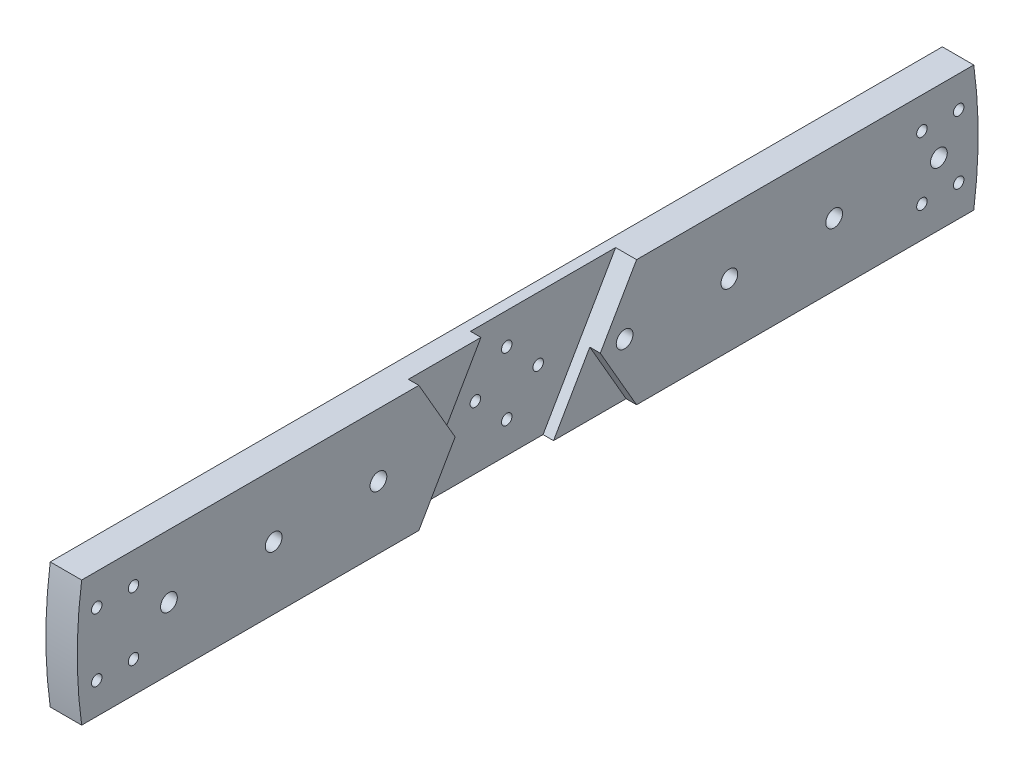
SolidWorks part; units mm, degrees
ref_plane "Front Plane" through (0, 0, 0) normal (0, 0, 1) x (1, 0, 0)
ref_plane "Top Plane" through (0, 0, 0) normal (0, 1, 0) x (1, 0, 0)
ref_plane "Right Plane" through (0, 0, 0) normal (1, 0, 0) x (0, 0, -1)
sketch "Sketch1" plane through (0, 0, 0) normal (1, 0, 0) x (0, 0, -1)
  circle A0 centre (0, 0) radius 273.05
  point P0 (0, 0)
  dimension "D1" = 546.1
curve "Helix/Spiral1"
sketch "Sketch2" plane through (0, 0, 0) normal (1, 0, 0) x (0, 0, -1)
  line L0 (-273.05, 0) -> (273.05, 0) construction
  line L1 (-270.3788, -38.1) -> (270.3788, -38.1)
  line L3 (-270.3788, 38.1) -> (270.3788, 38.1)
  line L4 (270.3788, -38.1) -> (270.3788, 38.1) construction
  line L5 (-270.3788, -38.1) -> (270.3788, 38.1) construction
  line L6 (-270.3788, 38.1) -> (270.3788, -38.1) construction
  line L7 (273.05, 0) -> (228.6, 0) construction
  line L8 (38.1, -38.1) -> (-38.1, -38.1)
  line L9 (38.1, -38.1) -> (38.1, 38.1)
  line L10 (38.1, 38.1) -> (-38.1, 38.1)
  line L11 (-38.1, -38.1) -> (-38.1, 38.1)
  line L12 (38.1, -38.1) -> (-38.1, 38.1) construction
  line L13 (38.1, 38.1) -> (-38.1, -38.1) construction
  line L14 (226.3636, 31.8977) -> (270.3788, 38.1)
  line L16 (273.05, 0) -> (250.825, 0)
  line L17 (250.825, 0) -> (228.6, 0)
  line L18 (0, 0) -> (238.9495, -19.1108) construction
  line L19 (0, 0) -> (-19.1108, -238.9495) construction
  line L20 (0, 38.1) -> (0, -38.1) construction
  line L21 (0, 0) -> (38.1, 38.1)
  line L28 (19.05, -19.05) -> (-19.05, -19.05)
  line L29 (19.05, -19.05) -> (19.05, 19.05)
  line L30 (19.05, 19.05) -> (-19.05, 19.05)
  line L31 (-19.05, -19.05) -> (-19.05, 19.05)
  line L32 (19.05, -19.05) -> (-19.05, 19.05) construction
  line L33 (19.05, 19.05) -> (-19.05, -19.05) construction
  circle A0 centre (0, 0) radius 273.05 construction
  circle A3 centre (185.7375, 0) radius 5.08
  circle A4 centre (122.2375, 0) radius 5.08
  circle A6 centre (-90.4875, 0) radius 5.08
  circle A7 centre (-153.9875, 0) radius 5.08
  circle A8 centre (-217.4875, 0) radius 5.08
  circle A9 centre (0, 0) radius 273.05
  circle A10 centre (0, 0) radius 228.6
  arc A11 (247.9144, -38.1) -> (250.825, 0) centre (0, 0) ccw
  arc A12 (236.6653, -38.1) -> (239.7125, 0) centre (0, 0) ccw
  arc A13 (259.1518, -38.1) -> (261.9375, 0) centre (0, 0) ccw
  circle A14 centre (238.9495, -19.1108) radius 3.175
  circle A15 centre (261.2401, -19.1009) radius 3.175
  circle A16 centre (238.9495, 19.1108) radius 3.175
  circle A17 centre (261.2401, 19.1009) radius 3.175
  circle A18 centre (19.1009, -261.2401) radius 3.175
  circle A19 centre (19.1108, -238.9495) radius 3.175
  circle A20 centre (-19.1108, -238.9495) radius 3.175
  circle A21 centre (-19.1009, -261.2401) radius 3.175
  circle A26 centre (-19.1009, 261.2401) radius 3.175
  circle A27 centre (-19.1108, 238.9495) radius 3.175
  circle A28 centre (19.1108, 238.9495) radius 3.175
  circle A29 centre (19.1009, 261.2401) radius 3.175
  circle A30 centre (-19.05, 0) radius 3.175
  circle A31 centre (0, 19.05) radius 3.175
  circle A32 centre (19.05, 0) radius 3.175
  circle A33 centre (0, -19.05) radius 3.175
  circle A34 centre (-238.9495, 19.1108) radius 3.175 [skipped]
  circle A35 centre (-261.2401, 19.1009) radius 3.175 [skipped]
  circle A36 centre (-261.2401, -19.1009) radius 3.175 [skipped]
  circle A37 centre (-238.9495, -19.1108) radius 3.175 [skipped]
  circle A38 centre (-261.2401, -19.1009) radius 3.175
  circle A39 centre (-238.9495, -19.1108) radius 3.175
  circle A40 centre (-238.9495, 19.1108) radius 3.175
  circle A41 centre (-261.2401, 19.1009) radius 3.175
  circle A42 centre (249.2375, 0) radius 5.08
  circle A43 centre (58.7375, 0) radius 5.08
  spline S0 degree 3 poles (2507.332, -531.0388) (-333.9741, -809.5147) (-458.8613, -7.3618) (-165.4997, 215.6959) (-158.1554, 220.7296) (-143.0366, 230.0361) (-135.2622, 234.3089) (-119.3613, 242.0581) (-111.2349, 245.5344) (-94.711, 251.6629) (-86.3136, 254.315) (-69.3307, 258.7755) (-60.7453, 260.5838) (-43.4707, 263.3455) (-34.7816, 264.2989) (-17.3841, 265.3477) (-8.6758, 265.4432) (8.6758, 264.7818) (17.319, 264.0248) (34.4576, 261.6722) (42.9529, 260.0765) (59.7146, 256.0679) (67.9811, 253.6551) (84.207, 248.0418) (92.1666, 244.8413) (107.7042, 237.6894) (115.2823, 233.7381) (129.9869, 225.1283) (137.1133, 220.4699) (150.8492, 210.4964) (157.4586, 205.1813) (170.1005, 193.9506) (176.133, 188.0351) (187.5674, 175.6653) (192.9692, 169.211) (203.0948, 155.8303) (207.8186, 148.9037) (220.9125, 127.5215) (228.2012, 112.4618) (239.6629, 81.3339) (243.8357, 65.2665) (248.9537, 32.7554) (249.899, 16.3126) (248.576, -16.3126) (246.3081, -32.494) (238.6964, -63.9794) (233.353, -79.2826) (219.8445, -108.438) (211.6799, -122.2896) (192.8873, -148.0335) (182.26, -159.9252) (158.9898, -181.3245) (146.3476, -190.8317) (119.5657, -207.1357) (105.4268, -213.9323) (76.2187, -224.5987) (61.1504, -228.4684) (30.6774, -233.1811) (15.2735, -234.024) (-15.2735, -232.701) (-30.416, -230.5354) (-59.8633, -223.3291) (-74.1674, -218.2888) (-101.403, -205.5756) (-114.3338, -197.903) (-138.3499, -180.2649) (-149.4346, -170.2999) (-169.3645, -148.4991) (-178.2093, -136.664) (-193.3589, -111.6099) (-199.6633, -98.3917) (-209.5345, -71.1035) (-213.1012, -57.0343) (-217.4084, -28.5994) (-218.149, -14.2345) (-216.826, 14.2345) (-214.7627, 28.338) (-207.9619, 55.7472) (-203.2246, 69.0522) (-191.3066, 94.368) (-184.1262, 106.3781) (-167.6426, 128.6663) (-158.3399, 138.944) (-138.0085, 157.4045) (-126.9804, 165.587) (-103.6542, 179.582) (-91.3567, 185.3943) (-65.9884, 194.4703) (-52.9182, 197.7339) (-26.5214, 201.6357) (-13.1955, 202.274) (13.1955, 200.951) (26.26, 198.9901) (51.631, 192.5946) (63.937, 188.1604) (87.3329, 177.0376) (98.4223, 170.3494) (118.9827, 155.0203) (128.4533, 146.3799) (145.4445, 127.5179) (152.9647, 117.2968) (165.8052, 95.6984) (171.1253, 84.3217) (179.4061, 60.8732) (182.3666, 48.8021) (185.8631, 24.4434) (186.399, 12.1565) (185.076, -12.1565) (183.2174, -24.182) (177.2273, -47.5149) (173.0962, -58.8219) (162.7686, -80.2979) (156.5725, -90.4665) (142.3979, -109.2991) (134.4199, -117.9627) (117.0273, -133.4845) (107.6132, -140.3423) (87.7426, -152.0284) (77.2867, -156.8564) (55.758, -164.3419) (44.6859, -166.9994) (22.3654, -170.0904) (11.1175, -170.524) (-11.1175, -169.201) (-22.104, -167.4447) (-43.3988, -161.8601) (-53.7067, -158.032) (-73.2629, -148.4997) (-82.5108, -142.7957) (-99.6156, -129.7756) (-107.4721, -122.4599) (-121.5244, -106.5366) (-127.72, -97.9296) (-138.2515, -79.7869) (-142.5874, -70.2516) (-149.2777, -50.6428) (-151.6321, -40.5698) (-154.3177, -20.2874) (-154.649, -10.0785) (-153.326, 10.0785) (-151.672, 20.026) (-146.4928, 39.2827) (-142.9678, 48.5915) (-134.2307, 66.2279) (-129.0189, 74.555) (-117.1533, 89.932) (-110.4999, 96.9815) (-96.046, 109.5644) (-88.246, 115.0977) (-71.8311, 124.4747) (-63.2166, 128.3184) (-45.5277, 134.2135) (-36.4537, 136.2649) (-18.2094, 138.545) (-9.0394, 138.774) (9.0394, 137.451) (17.948, 135.8994) (35.1666, 131.1255) (43.4763, 127.9036) (59.1928, 119.9617) (66.5992, 115.2421) (80.2484, 104.5309) (86.4908, 98.5398) (97.6044, 85.5554) (102.4753, 78.5625) (110.6979, 63.8753) (114.0494, 56.1816) (119.1493, 40.4125) (120.8976, 32.3376) (122.7724, 16.1314) (122.899, 8.0004) (121.576, -8.0004) (120.1267, -15.8699) (115.7583, -31.0505) (112.8394, -38.3612) (105.6927, -52.1578) (101.4652, -58.6435) (91.9086, -70.5648) (86.5798, -76.0002) (75.0648, -85.6444) (68.8789, -89.853) (55.9196, -96.9211) (49.1466, -99.7805) (35.2973, -104.0851) (28.2215, -105.5303) (14.0534, -106.9997) (6.9614, -107.024) (-6.9614, -105.701) (-13.7919, -104.354) (-26.9344, -100.391) (-33.246, -97.7752) (-45.1228, -91.4238) (-50.6877, -87.6884) (-60.8812, -79.2863) (-65.5096, -74.6198) (-73.6844, -64.5742) (-77.2307, -59.1953) (-83.1442, -47.9638) (-85.5115, -42.1115) (-89.0209, -30.1822) (-90.1631, -24.1054) (-91.227, -11.9753) (-91.149, -5.9224) (-89.826, 5.9224) (-88.5814, 11.7139) (-85.0237, 22.8183) (-82.711, 28.1308) (-77.1548, 38.0878) (-73.9116, 42.7319) (-66.6639, 51.1976) (-62.6598, 55.019) (-54.0835, 61.7244) (-49.5117, 64.6083) (-40.008, 69.3674) (-35.0765, 71.2425) (-25.067, 73.9567) (-19.9893, 74.7958) (-9.8973, 75.4544) (-4.8834, 75.274) (4.8834, 73.951) (9.6359, 72.8087) (18.7022, 69.6565) (23.0157, 67.6468) (31.0527, 62.8858) (34.7762, 60.1348) (41.514, 54.0416) (44.5283, 50.6998) (49.7643, 43.5929) (51.986, 39.8281) (55.5906, 32.0523) (56.9736, 28.0415) (58.8925, 19.9518) (59.4285, 15.8732) (59.6817, 7.8193) (59.399, 3.8444) (58.076, -3.8444) (57.036, -7.5579) (54.2892, -14.5861) (52.5826, -17.9005) (48.6168, -24.0177) (46.3579, -26.8204) (41.4193, -31.8304) (38.7398, -34.0377) (33.1023, -37.8043) (30.1445, -39.3637) (24.0965, -41.8138) (21.0065, -42.7046) (14.8366, -43.8283) (11.7571, -44.0613) (5.7413, -43.909) (2.8053, -43.524) (-2.8053, -42.201) (-5.4799, -41.2634) (-10.4699, -38.922) (-12.7853, -37.5184) (-16.9827, -34.3479) (-18.8646, -32.5811) (-22.1469, -28.7969) (-23.5471, -26.7798) (-25.8443, -22.6117) (-26.7413, -20.4609) (-28.0369, -16.1407) (-28.4356, -13.9714) (-28.7641, -9.7215) (-28.694, -7.6409) (-28.1364, -3.6633) (-27.649, -1.7663) (-26.326, 1.7663) (-25.4907, 3.4019) (-23.5547, 6.3538) (-22.4542, 7.6701) (-20.0789, 9.9477) (-18.8043, 10.9089) (37.39, 44.1251) (162.0147, -243.9693) (-2955.5426, -510.8327) knots -0.153771 -0.153771 -0.153771 -0.153771 0.003906 0.003906 0.007812 0.007812 0.011719 0.011719 0.015625 0.015625 0.019531 0.019531 0.023438 0.023438 0.027344 0.027344 0.03125 0.03125 0.035156 0.035156 0.039062 0.039062 0.042969 0.042969 0.046875 0.046875 0.050781 0.050781 0.054688 0.054688 0.058594 0.058594 0.0625 0.0625 0.066406 0.066406 0.070312 0.070312 0.078125 0.078125 0.085938 0.085938 0.09375 0.09375 0.101562 0.101562 0.109375 0.109375 0.117188 0.117188 0.125 0.125 0.132812 0.132812 0.140625 0.140625 0.148438 0.148438 0.15625 0.15625 0.164062 0.164062 0.171875 0.171875 0.179688 0.179688 0.1875 0.1875 0.195312 0.195312 0.203125 0.203125 0.210938 0.210938 0.21875 0.21875 0.226562 0.226562 0.234375 0.234375 0.242188 0.242188 0.25 0.25 0.257812 0.257812 0.265625 0.265625 0.273438 0.273438 0.28125 0.28125 0.289062 0.289062 0.296875 0.296875 0.304688 0.304688 0.3125 0.3125 0.320312 0.320312 0.328125 0.328125 0.335938 0.335938 0.34375 0.34375 0.351562 0.351562 0.359375 0.359375 0.367188 0.367188 0.375 0.375 0.382812 0.382812 0.390625 0.390625 0.398438 0.398438 0.40625 0.40625 0.414062 0.414062 0.421875 0.421875 0.429688 0.429688 0.4375 0.4375 0.445312 0.445312 0.453125 0.453125 0.460938 0.460938 0.46875 0.46875 0.476562 0.476562 0.484375 0.484375 0.492188 0.492188 0.5 0.5 0.507812 0.507812 0.515625 0.515625 0.523438 0.523438 0.53125 0.53125 0.539062 0.539062 0.546875 0.546875 0.554688 0.554688 0.5625 0.5625 0.570312 0.570312 0.578125 0.578125 0.585938 0.585938 0.59375 0.59375 0.601562 0.601562 0.609375 0.609375 0.617188 0.617188 0.625 0.625 0.632812 0.632812 0.640625 0.640625 0.648438 0.648438 0.65625 0.65625 0.664062 0.664062 0.671875 0.671875 0.679688 0.679688 0.6875 0.6875 0.695312 0.695312 0.703125 0.703125 0.710938 0.710938 0.71875 0.71875 0.726562 0.726562 0.734375 0.734375 0.742188 0.742188 0.75 0.75 0.757812 0.757812 0.765625 0.765625 0.773438 0.773438 0.78125 0.78125 0.789062 0.789062 0.796875 0.796875 0.804688 0.804688 0.8125 0.8125 0.820312 0.820312 0.828125 0.828125 0.835938 0.835938 0.84375 0.84375 0.851562 0.851562 0.859375 0.859375 0.867188 0.867188 0.875 0.875 0.882812 0.882812 0.890625 0.890625 0.898438 0.898438 0.90625 0.90625 0.914062 0.914062 0.921875 0.921875 0.929688 0.929688 0.9375 0.9375 0.945312 0.945312 0.953125 0.953125 0.960938 0.960938 0.96875 0.96875 0.976562 0.976562 0.984375 0.984375 0.992188 0.992188 1.318271 1.318271 1.318271 1.318271 only from (-193.0755, 193.0755) to (-13.4704, 13.4704) construction
  spline S1 degree 3 poles (-193.0755, 193.0755) (-186.5233, 199.16) (-179.6836, 204.9111) (-165.4997, 215.6959) (-158.1554, 220.7296) (-143.0366, 230.0361) (-135.2622, 234.3089) (-119.3613, 242.0581) (-111.2349, 245.5344) (-94.711, 251.6629) (-86.3136, 254.315) (-69.3307, 258.7755) (-60.7453, 260.5838) (-43.4707, 263.3455) (-34.7816, 264.2989) (-17.3841, 265.3477) (-8.6758, 265.4432) (8.6758, 264.7818) (17.319, 264.0248) (34.4576, 261.6722) (42.9529, 260.0765) (59.7146, 256.0679) (67.9811, 253.6551) (84.207, 248.0418) (92.1666, 244.8413) (107.7042, 237.6894) (115.2823, 233.7381) (129.9869, 225.1283) (137.1133, 220.4699) (150.8492, 210.4964) (157.4586, 205.1813) (170.1005, 193.9506) (176.133, 188.0351) (187.5674, 175.6653) (192.9692, 169.211) (203.0948, 155.8303) (207.8186, 148.9037) (220.9125, 127.5215) (228.2012, 112.4618) (239.6629, 81.3339) (243.8357, 65.2665) (248.9537, 32.7554) (249.899, 16.3126) (248.576, -16.3126) (246.3081, -32.494) (238.6964, -63.9794) (233.353, -79.2826) (219.8445, -108.438) (211.6799, -122.2896) (192.8873, -148.0335) (182.26, -159.9252) (158.9898, -181.3245) (146.3476, -190.8317) (119.5657, -207.1357) (105.4268, -213.9323) (76.2187, -224.5987) (61.1504, -228.4684) (30.6774, -233.1811) (15.2735, -234.024) (-15.2735, -232.701) (-30.416, -230.5354) (-59.8633, -223.3291) (-74.1674, -218.2888) (-101.403, -205.5756) (-114.3338, -197.903) (-138.3499, -180.2649) (-149.4346, -170.2999) (-169.3645, -148.4991) (-178.2093, -136.664) (-193.3589, -111.6099) (-199.6633, -98.3917) (-209.5345, -71.1035) (-213.1012, -57.0343) (-217.4084, -28.5994) (-218.149, -14.2345) (-216.826, 14.2345) (-214.7627, 28.338) (-207.9619, 55.7472) (-203.2246, 69.0522) (-191.3066, 94.368) (-184.1262, 106.3781) (-167.6426, 128.6663) (-158.3399, 138.944) (-138.0085, 157.4045) (-126.9804, 165.587) (-103.6542, 179.582) (-91.3567, 185.3943) (-65.9884, 194.4703) (-52.9182, 197.7339) (-26.5214, 201.6357) (-13.1955, 202.274) (13.1955, 200.951) (26.26, 198.9901) (51.631, 192.5946) (63.937, 188.1604) (87.3329, 177.0376) (98.4223, 170.3494) (118.9827, 155.0203) (128.4533, 146.3799) (145.4445, 127.5179) (152.9647, 117.2968) (165.8052, 95.6984) (171.1253, 84.3217) (179.4061, 60.8732) (182.3666, 48.8021) (185.8631, 24.4434) (186.399, 12.1565) (185.076, -12.1565) (183.2174, -24.182) (177.2273, -47.5149) (173.0962, -58.8219) (162.7686, -80.2979) (156.5725, -90.4665) (142.3979, -109.2991) (134.4199, -117.9627) (117.0273, -133.4845) (107.6132, -140.3423) (87.7426, -152.0284) (77.2867, -156.8564) (55.758, -164.3419) (44.6859, -166.9994) (22.3654, -170.0904) (11.1175, -170.524) (-11.1175, -169.201) (-22.104, -167.4447) (-43.3988, -161.8601) (-53.7067, -158.032) (-73.2629, -148.4997) (-82.5108, -142.7957) (-99.6156, -129.7756) (-107.4721, -122.4599) (-121.5244, -106.5366) (-127.72, -97.9296) (-138.2515, -79.7869) (-142.5874, -70.2516) (-149.2777, -50.6428) (-151.6321, -40.5698) (-154.3177, -20.2874) (-154.649, -10.0785) (-153.326, 10.0785) (-151.672, 20.026) (-146.4928, 39.2827) (-142.9678, 48.5915) (-134.2307, 66.2279) (-129.0189, 74.555) (-117.1533, 89.932) (-110.4999, 96.9815) (-96.046, 109.5644) (-88.246, 115.0977) (-71.8311, 124.4747) (-63.2166, 128.3184) (-45.5277, 134.2135) (-36.4537, 136.2649) (-18.2094, 138.545) (-9.0394, 138.774) (9.0394, 137.451) (17.948, 135.8994) (35.1666, 131.1255) (43.4763, 127.9036) (59.1928, 119.9617) (66.5992, 115.2421) (80.2484, 104.5309) (86.4908, 98.5398) (97.6044, 85.5554) (102.4753, 78.5625) (110.6979, 63.8753) (114.0494, 56.1816) (119.1493, 40.4125) (120.8976, 32.3376) (122.7724, 16.1314) (122.899, 8.0004) (121.576, -8.0004) (120.1267, -15.8699) (115.7583, -31.0505) (112.8394, -38.3612) (105.6927, -52.1578) (101.4652, -58.6435) (91.9086, -70.5648) (86.5798, -76.0002) (75.0648, -85.6444) (68.8789, -89.853) (55.9196, -96.9211) (49.1466, -99.7805) (35.2973, -104.0851) (28.2215, -105.5303) (14.0534, -106.9997) (6.9614, -107.024) (-6.9614, -105.701) (-13.7919, -104.354) (-26.9344, -100.391) (-33.246, -97.7752) (-45.1228, -91.4238) (-50.6877, -87.6884) (-60.8812, -79.2863) (-65.5096, -74.6198) (-73.6844, -64.5742) (-77.2307, -59.1953) (-83.1442, -47.9638) (-85.5115, -42.1115) (-89.0209, -30.1822) (-90.1631, -24.1054) (-91.227, -11.9753) (-91.149, -5.9224) (-89.826, 5.9224) (-88.5814, 11.7139) (-85.0237, 22.8183) (-82.711, 28.1308) (-77.1548, 38.0878) (-73.9116, 42.7319) (-66.6639, 51.1976) (-62.6598, 55.019) (-54.0835, 61.7244) (-49.5117, 64.6083) (-40.008, 69.3674) (-35.0765, 71.2425) (-25.067, 73.9567) (-19.9893, 74.7958) (-9.8973, 75.4544) (-4.8834, 75.274) (4.8834, 73.951) (9.6359, 72.8087) (18.7022, 69.6565) (23.0157, 67.6468) (31.0527, 62.8858) (34.7762, 60.1348) (41.514, 54.0416) (44.5283, 50.6998) (49.7643, 43.5929) (51.986, 39.8281) (55.5906, 32.0523) (56.9736, 28.0415) (58.8925, 19.9518) (59.4285, 15.8732) (59.6817, 7.8193) (59.399, 3.8444) (58.076, -3.8444) (57.036, -7.5579) (54.2892, -14.5861) (52.5826, -17.9005) (48.6168, -24.0177) (46.3579, -26.8204) (41.4193, -31.8304) (38.7398, -34.0377) (33.1023, -37.8043) (30.1445, -39.3637) (24.0965, -41.8138) (21.0065, -42.7046) (14.8366, -43.8283) (11.7571, -44.0613) (5.7413, -43.909) (2.8053, -43.524) (-2.8053, -42.201) (-5.4799, -41.2634) (-10.4699, -38.922) (-12.7853, -37.5184) (-16.9827, -34.3479) (-18.8646, -32.5811) (-22.1469, -28.7969) (-23.5471, -26.7798) (-25.8443, -22.6117) (-26.7413, -20.4609) (-28.0369, -16.1407) (-28.4356, -13.9714) (-28.7641, -9.7215) (-28.694, -7.6409) (-28.1364, -3.6633) (-27.649, -1.7663) (-26.326, 1.7663) (-25.4907, 3.4019) (-23.5547, 6.3538) (-22.4542, 7.6701) (-20.0789, 9.9477) (-18.8043, 10.9089) (-16.1746, 12.4633) (-14.8197, 13.0565) (-13.4704, 13.4704) knots 0 0 0 0 0.003906 0.003906 0.007812 0.007812 0.011719 0.011719 0.015625 0.015625 0.019531 0.019531 0.023438 0.023438 0.027344 0.027344 0.03125 0.03125 0.035156 0.035156 0.039062 0.039062 0.042969 0.042969 0.046875 0.046875 0.050781 0.050781 0.054688 0.054688 0.058594 0.058594 0.0625 0.0625 0.066406 0.066406 0.070312 0.070312 0.078125 0.078125 0.085938 0.085938 0.09375 0.09375 0.101562 0.101562 0.109375 0.109375 0.117188 0.117188 0.125 0.125 0.132812 0.132812 0.140625 0.140625 0.148438 0.148438 0.15625 0.15625 0.164062 0.164062 0.171875 0.171875 0.179688 0.179688 0.1875 0.1875 0.195312 0.195312 0.203125 0.203125 0.210938 0.210938 0.21875 0.21875 0.226562 0.226562 0.234375 0.234375 0.242188 0.242188 0.25 0.25 0.257812 0.257812 0.265625 0.265625 0.273438 0.273438 0.28125 0.28125 0.289062 0.289062 0.296875 0.296875 0.304688 0.304688 0.3125 0.3125 0.320312 0.320312 0.328125 0.328125 0.335938 0.335938 0.34375 0.34375 0.351562 0.351562 0.359375 0.359375 0.367188 0.367188 0.375 0.375 0.382812 0.382812 0.390625 0.390625 0.398438 0.398438 0.40625 0.40625 0.414062 0.414062 0.421875 0.421875 0.429688 0.429688 0.4375 0.4375 0.445312 0.445312 0.453125 0.453125 0.460938 0.460938 0.46875 0.46875 0.476562 0.476562 0.484375 0.484375 0.492188 0.492188 0.5 0.5 0.507812 0.507812 0.515625 0.515625 0.523438 0.523438 0.53125 0.53125 0.539062 0.539062 0.546875 0.546875 0.554688 0.554688 0.5625 0.5625 0.570312 0.570312 0.578125 0.578125 0.585938 0.585938 0.59375 0.59375 0.601562 0.601562 0.609375 0.609375 0.617188 0.617188 0.625 0.625 0.632812 0.632812 0.640625 0.640625 0.648438 0.648438 0.65625 0.65625 0.664062 0.664062 0.671875 0.671875 0.679688 0.679688 0.6875 0.6875 0.695312 0.695312 0.703125 0.703125 0.710938 0.710938 0.71875 0.71875 0.726562 0.726562 0.734375 0.734375 0.742188 0.742188 0.75 0.75 0.757812 0.757812 0.765625 0.765625 0.773438 0.773438 0.78125 0.78125 0.789062 0.789062 0.796875 0.796875 0.804688 0.804688 0.8125 0.8125 0.820312 0.820312 0.828125 0.828125 0.835938 0.835938 0.84375 0.84375 0.851562 0.851562 0.859375 0.859375 0.867188 0.867188 0.875 0.875 0.882812 0.882812 0.890625 0.890625 0.898438 0.898438 0.90625 0.90625 0.914062 0.914062 0.921875 0.921875 0.929688 0.929688 0.9375 0.9375 0.945312 0.945312 0.953125 0.953125 0.960938 0.960938 0.96875 0.96875 0.976562 0.976562 0.984375 0.984375 0.992188 0.992188 1 1 1 1 construction
  point P0 (0, 0)
  point P26 (0, 0)
  point P37 (250.825, 0)
  point P40 (239.7125, 0)
  point P45 (261.9375, 0)
  point P46 (238.9495, -19.1108)
  point P64 (261.2401, -19.1009)
  point P85 (19.05, 19.05)
  point P98 (-24.6957, -24.6956)
  point P99 (-24.6957, -24.6957)
  dimension "D2" = 10.16
  dimension "D4" = 457.2
  dimension "D5" = 6.35
  dimension "D9" = 6.35
  dimension "D1" = 76.2
  dimension "D3" = 76.2
  dimension "D7" = 90
  dimension "D8" = 239.7125
  dimension "D6" = 4
extrude "Boss-Extrude1" add sketch "Sketch2" along normal blind 19.05 contours L3 A10 L1 L11 A6 A7 A8 | A10 L3 L9 L1 A3 A4 | A15 A13 L1 A9 L14 A10 L17 L16 A16 A17 | A10 L14 L3 | A14 A12 L17 A10 L1 | A14 A12 L1 A11 L17 | A15 A13 L16 A11 L1 | A15 A13 L1 A9 L16 | A10 L3 A9 L1 A41 A40 A38 A39 | L9 L8 L11 L10 | A30 | A32 | A33 | A31 region at (0, 0, 132.4583) region at (0, 0, -133.0024) region at (0, 0, 249.8366) region at (0, -19.096, -232.9415) region at (0, -20.3261, -244.1734) region at (0, 17.9363, -250.725) region at (0, 36.0332, -240.7246) region at (0, -19.078, -266.739) region at (0, -19.6249, -255.3526)
sketch "Sketch3" plane through (19.05, 0, 0) normal (1, 0, 0) x (0, 0, -1)
  line L0 (-270.3788, 38.1) -> (270.3788, 38.1) construction
  line L1 (38.1, -38.1) -> (-38.1, -38.1)
  line L2 (38.1, -38.1) -> (38.1, 38.1)
  line L3 (38.1, 38.1) -> (-38.1, 38.1)
  line L4 (-38.1, -38.1) -> (-38.1, 38.1)
  line L5 (38.1, -38.1) -> (-38.1, 38.1) construction
  line L6 (38.1, 38.1) -> (-38.1, -38.1) construction
  line L7 (-65.9911, -38.1) -> (21.997, -38.1)
  line L8 (-65.9911, -38.1) -> (-21.997, 38.1)
  line L9 (21.997, -38.1) -> (65.9911, 38.1)
  line L10 (-21.997, 38.1) -> (65.9911, 38.1)
  line L11 (-270.3788, -38.1) -> (270.3788, -38.1) construction
  line L12 (-21.997, 38.1) -> (21.997, -38.1) construction
  line L13 (0, 300.355) -> (0, -300.355) construction
  line L14 (-21.997, -38.1) -> (-65.9911, 38.1)
  line L15 (21.997, 38.1) -> (-65.9911, 38.1)
  line L16 (65.9911, -38.1) -> (21.997, 38.1)
  line L17 (65.9911, -38.1) -> (-21.997, -38.1)
  point P0 (0, 0)
  point P14 (0, 0)
  line M13 (270.3788, 38.1) -> (-270.3788, 38.1)
  line M15 (-270.3788, -38.1) -> (270.3788, -38.1)
  circle M22 centre (-19.05, 0) radius 3.175
  circle M23 centre (19.05, 0) radius 3.175
  circle M24 centre (0, -19.05) radius 3.175
  circle M25 centre (0, 19.05) radius 3.175
  dimension "D1" = 76.2
  dimension "D2" = 76.2
  dimension "D3" = 60
extrude "Cut-Extrude1" cut sketch "Sketch3" against normal blind 12.7 contours L4 L14 L8 M15 | L14 L4 L8 | L2 L16 L10 L8 L4 L14 L7 L9 M23 M25 M24 M22 | L14 L4 M15 | L16 L2 L9 | L16 L9 L2 M13 | L16 L2 M13 region at (19.05, 0, 0) region at (19.05, 0, -40.0647) region at (19.05, -28.803, 32.7323) region at (19.05, 28.803, -32.7323) region at (19.05, 24.1544, -48.1162) region at (19.05, -24.1544, 48.1162) region at (19.05, 0, 40.0647)
extrude "Cut-Extrude2" cut sketch "Sketch3<3>" against normal blind 6.35 contours L14 L8 L4 M13 | L4 L8 L3 | L9 L1 L2 | L16 L9 L2 M15 region at (19.05, -28.803, -32.7323) region at (19.05, -24.1544, -48.1162) region at (19.05, 24.1544, 48.1162) region at (19.05, 28.803, 32.7323)
sketch "Sketch3<3>" plane through (19.05, 0, 0) normal (1, 0, 0) x (0, 0, -1) same geometry as "Sketch3"
